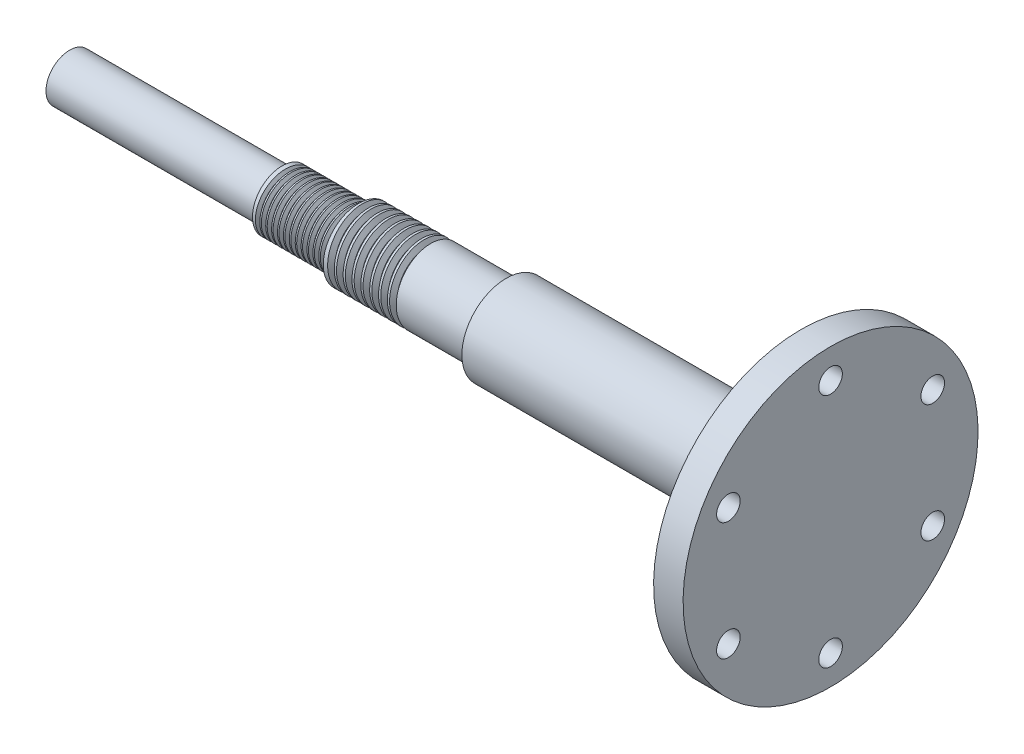
SolidWorks part; units mm, degrees
material "6061-T6 (SS)"
ref_plane "Front Plane" through (0, 0, 0) normal (0, 0, 1) x (1, 0, 0)
ref_plane "Top Plane" through (0, 0, 0) normal (0, 1, 0) x (1, 0, 0)
ref_plane "Right Plane" through (0, 0, 0) normal (1, 0, 0) x (0, 0, -1)
sketch "Sketch1" plane through (0, 0, 0) normal (0, 0, 1) x (1, 0, 0)
  line L0 (0, 11.579) -> (0, 19.079)
  line L1 (0, 19.079) -> (50, 19.079)
  line L2 (50, 19.079) -> (50, 36.579)
  line L3 (50, 36.579) -> (55, 36.579)
  line L4 (55, 36.579) -> (55, 11.579)
  line L5 (55, 11.579) -> (0, 11.579)
  dimension "D1" = 7.5
  dimension "D2" = 25
  dimension "D3" = 55
  dimension "D4" = 5
revolve "Revolve1" add sketch "Sketch1" angle 360 about L5
sketch "Sketch2" plane through (55, 0, 0) normal (1, 0, 0) x (0, 0, -1)
  circle A0 centre (0, 11.579) radius 25 construction
  circle A1 centre (0, 11.579) radius 20 construction
  circle A2 centre (0, 31.579) radius 2
  circle A3 centre (17.3205, 21.579) radius 2
  circle A4 centre (17.3205, 1.579) radius 2
  circle A5 centre (0, -8.421) radius 2
  circle A6 centre (-17.3205, 1.579) radius 2
  circle A7 centre (-17.3205, 21.579) radius 2
  point P18 (0, 11.579)
  dimension "D1" = 40
  dimension "D2" = 4
  dimension "D3" = 6
extrude "Cut-Extrude1" cut sketch "Sketch2" against normal blind 10
sketch "Sketch3" plane through (0, 0, 0) normal (-1, 0, 0) x (0, 0, 1)
  circle A0 centre (0, 11.579) radius 6
  dimension "D1" = 12
extrude "Boss-Extrude1" add sketch "Sketch3" along normal blind 25
sketch "Sketch4" plane through (-25, 0, 0) normal (-1, 0, 0) x (0, 0, 1)
  circle A0 centre (0, 11.579) radius 5
  dimension "D1" = 10
extrude "Boss-Extrude2" add sketch "Sketch4" along normal blind 13
sketch "Sketch5" plane through (-38, 0, 0) normal (-1, 0, 0) x (0, 0, 1)
  circle A0 centre (0, 11.579) radius 4
  dimension "D1" = 8
extrude "Boss-Extrude3" add sketch "Sketch5" along normal blind 36
thread "Thread1" pitch 1.5 start angle 0, offset 0, length 12, pitch 1.5, diameter 12
ref_plane "Plane1" through (-25, 11.579, -6) normal (0, 1, 0) x (0, 0, 1)
sketch "Thread Profile1" plane through (-25, 11.579, -6) normal (0, 1, 0) x (0, 0, 1)
  line L0 (0, 0) -> (0, 1.5) construction
  line L1 (0, 0) -> (0.8119, 0.4687)
  line L2 (0.8119, 0.4687) -> (0.8119, 0.6562)
  line L3 (0.8119, 0.6562) -> (0, 1.125)
  line L4 (0.8119, 0.5625) -> (0, 0.5625) construction
  line L11 (0, 0) -> (0, 1.125)
  point P2 (0, 0)
  dimension "Pitch" = 1.5
  dimension "Profile_Angle" = 60
  dimension "Profile_Land" = 0.1875
  dimension "Profile_Height" = 0.8119
thread "Thread2" start angle 0, offset 0, length 12, pitch 1, diameter 10
ref_plane "Plane2" through (-38, 11.579, -5) normal (0, 1, 0) x (0, 0, 1)
sketch "Thread Profile2" plane through (-38, 11.579, -5) normal (0, 1, 0) x (0, 0, 1)
  line L0 (0, 0) -> (0, 1) construction
  line L1 (0, 0) -> (0.5413, 0.3125)
  line L2 (0.5413, 0.3125) -> (0.5413, 0.4375)
  line L3 (0.5413, 0.4375) -> (0, 0.75)
  line L4 (0.5413, 0.375) -> (0, 0.375) construction
  line L11 (0, 0) -> (0, 0.75)
  point P2 (0, 0)
  dimension "Pitch" = 1
  dimension "Profile_Angle" = 60
  dimension "Profile_Land" = 0.125
  dimension "Profile_Height" = 0.5413
